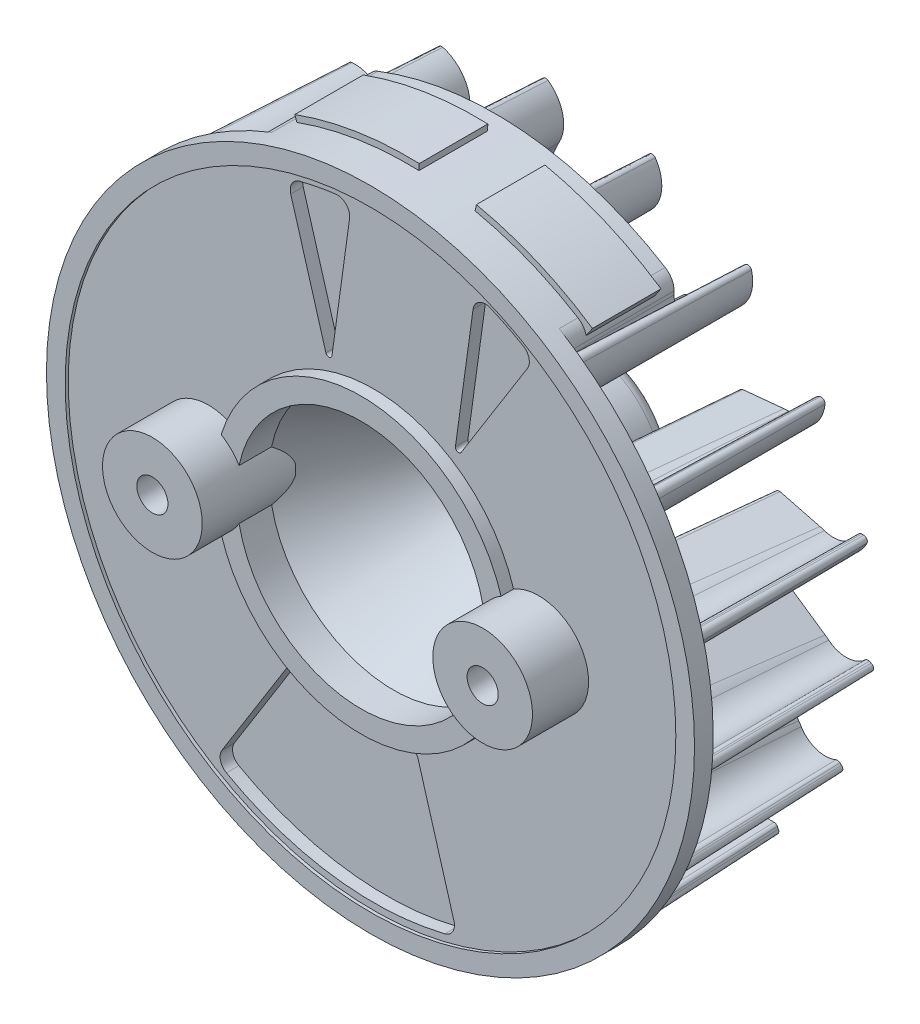
SolidWorks part; units mm, degrees
note: '?' marks a value the reader was unsure of.
ref_plane "Plan1" through (0, 0, 0) normal (0, 0, 1) x (1, 0, 0)
ref_plane "Plan2" through (0, 0, 0) normal (0, 1, 0) x (1, 0, 0)
ref_plane "Plan3" through (0, 0, 0) normal (1, 0, 0) x (0, 0, -1)
sketch "Esquisse1" plane through (0, 0, 0) normal (0, 0, 1) x (1, 0, 0)
  circle A0 centre (0, 0) radius 13
  dimension "D1" = 26
extrude "Base-Extrusion" add sketch "Esquisse1" along normal blind 33
sketch "Esquisse2" plane through (0, 0, 33) normal (0, 0, 1) x (1, 0, 0)
  circle A0 centre (0, 0) radius 52
  dimension "D1" = 104
extrude "Boss.-Extru.1" add sketch "Esquisse2" along normal blind 3
sketch "Esquisse3" plane through (0, 0, 33) normal (0, 0, -1) x (-1, 0, 0)
  line L0 (2.2116, 39.1745) -> (4.5884, 33.9114)
  line L1 (3.9578, 40.1672) -> (6.4523, 34.6434)
  line L2 (4.3511, 50.3505) -> (4.3846, 50.1223)
  line L3 (5.9114, 33.4116) -> (6.0025, 33.4527)
  arc A0 (2.9098, 50.9313) -> (1.3276, 40.7395) centre (7.5, 45) ccw
  arc A1 (4.3511, 50.3505) -> (2.9098, 50.9313) centre (3.4607, 50.2195) ccw
  arc A2 (4.0575, 49.2895) -> (3.0092, 41.8247) centre (7.5, 45) ccw
  arc A3 (4.0575, 49.2895) -> (4.3846, 50.1223) centre (3.4942, 49.9914) ccw
  arc A5 (5.9114, 33.4116) -> (4.5884, 33.9114) centre (5.4998, 34.323) cw
  arc A6 (6.4523, 34.6434) -> (6.0025, 33.4527) centre (5.6321, 34.273) cw
  arc A7 (2.2116, 39.1745) -> (1.3276, 40.7395) centre (-6.9022, 35.0588) ccw
  arc A8 (3.9578, 40.1672) -> (3.0092, 41.8247) centre (-5.1559, 36.0514) ccw
  point P12 (4.3707, 51.816)
  point P17 (5, 33)
  dimension "D3" = 15
  dimension "D7" = 0.9
  dimension "D8" = 1
  dimension "D9" = 0.9
  dimension "D10" = 10
  dimension "D1" = 45
  dimension "D2" = 7.5
  dimension "D4" = 5
  dimension "D5" = 33
  dimension "D6" = 2
ref_plane "Plan4" through (0, 0, 5) normal (0, 0, -1) x (-1, 0, 0)
sketch "Esquisse4" plane through (0, 0, 5) normal (0, 0, -1) x (-1, 0, 0)
  line L0 (1.1226, 41.3554) -> (3.7525, 35.5466)
  line L2 (4.5466, 35.2475) -> (4.8199, 35.3712)
  line L3 (3.4375, 49.5018) -> (3.5019, 49.1763)
  line L4 (5.1185, 36.1663) -> (2.3802, 42.1843)
  arc A0 (2.4988, 49.8725) -> (0.7548, 42.0866) centre (6, 45) ccw
  arc A1 (3.2765, 48.5822) -> (2.0519, 42.8408) centre (6, 45) ccw
  arc A2 (3.4375, 49.5018) -> (2.4988, 49.8725) centre (2.8489, 49.3853) ccw
  arc A3 (3.2765, 48.5822) -> (3.5019, 49.1763) centre (2.9133, 49.0598) ccw
  arc A4 (4.8199, 35.3712) -> (5.1185, 36.1663) centre (4.5724, 35.9178) ccw
  arc A5 (3.7525, 35.5466) -> (4.5466, 35.2475) centre (4.2991, 35.7941) ccw
  arc A6 (0.7548, 42.0866) -> (1.1226, 41.3554) centre (-7.9872, 37.231) cw
  arc A7 (2.0519, 42.8408) -> (2.3802, 42.1843) centre (-6.7218, 38.0426) cw
  point P18 (4, 35)
  dimension "D1" = 12
  dimension "D2" = 45
  dimension "D3" = 6
  dimension "D7" = 0.6
  dimension "D8" = 0.6
  dimension "D9" = 10
  dimension "D10" = 10
  dimension "D4" = 35
  dimension "D5" = 4
  dimension "D6" = 1.5
loft "Boss.-Lissage1" add profiles "Esquisse3", "Esquisse4"
ref_axis "Axe1" through (0, 0, -50) along (0, 0, 1)?
pattern_circular "Répétition circulaire1" count 18 over 360 about axis through (0, 0, -50) along (0, 0, 1)
sketch "Esquisse6" plane through (0, 0, 33) normal (0, 0, -1) x (-1, 0, 0)
  line L0 (-24.8935, 34.1273) -> (-16.7651, 28.6384)
  line L1 (-28.7181, 41.1538) -> (-28.7181, 41.7082)
  line L2 (20.7305, 45.6796) -> (20.7305, 45.5102)
  line L3 (15.8737, 39.3222) -> (10.1445, 31.2739)
  line L4 (-24, 39) -> (20.7305, 40.5102) construction
  line L5 (0, 0) -> (-4.0114, 39.6749) construction
  line L6 (9.2432, 27.8713) -> (14.5886, -24.9977)
  line L7 (-9.2432, -27.8713) -> (-14.5886, 24.9977)
  line L9 (24.8935, -34.1273) -> (16.7651, -28.6384)
  line L10 (28.7181, -40.9224) -> (28.7181, -41.7082)
  line L11 (-20.7305, -45.6796) -> (-20.7305, -45.5102)
  line L12 (-15.8737, -39.3222) -> (-10.1445, -31.2739)
  line L16 (24, -39) -> (-20.7305, -40.5102) construction
  line L17 (0, 0) -> (4.0114, -39.6749) construction
  arc A0 (-28.8366, 40.0719) -> (-24.8935, 34.1273) centre (-24, 39) ccw
  arc A1 (18.8161, 48.4763) -> (-27.2927, 44.2618) centre (0, 0) ccw
  arc A2 (20.7305, 45.5102) -> (15.8737, 39.3222) centre (20.7305, 40.5102) ccw
  arc A3 (28.8071, -40.1973) -> (24.8935, -34.1273) centre (24, -39) ccw
  arc A4 (-18.8161, -48.4763) -> (27.2927, -44.2618) centre (0, 0) ccw
  arc A5 (-20.7305, -45.5102) -> (-15.8737, -39.3222) centre (-20.7305, -40.5102) ccw
  arc A6 (-28.7181, 41.1538) -> (-28.8366, 40.0719) centre (-33.7181, 41.1538) cw
  arc A7 (-27.2927, 44.2618) -> (-28.7181, 41.7082) centre (-25.7181, 41.7082) ccw
  arc A8 (-14.5886, 24.9977) -> (-16.7651, 28.6384) centre (-19.5632, 24.4947) ccw
  arc A9 (-10.1445, -31.2739) -> (-9.2432, -27.8713) centre (-14.2178, -28.3742) ccw
  arc A10 (-18.8161, -48.4763) -> (-20.7305, -45.6796) centre (-17.7305, -45.6796) cw
  arc A11 (28.7181, -41.7082) -> (27.2927, -44.2618) centre (25.7181, -41.7082) cw
  arc A12 (28.8071, -40.1973) -> (28.7181, -40.9224) centre (31.7181, -40.9224) ccw
  arc A13 (14.5886, -24.9977) -> (16.7651, -28.6384) centre (19.5632, -24.4947) ccw
  arc A14 (10.1445, 31.2739) -> (9.2432, 27.8713) centre (14.2178, 28.3742) ccw
  arc A15 (18.8161, 48.4763) -> (20.7305, 45.6796) centre (17.7305, 45.6796) cw
  point P33 (-14.8242, 27.3278)
  point P45 (9.0541, 29.742)
  dimension "D1" = 10
  dimension "D4" = 5
  dimension "D5" = 3
  dimension "D6" = 5
  dimension "D7" = 3
  dimension "D8" = 5
  dimension "D9" = 3
  dimension "D2" = 44.756
  dimension "D3" = 20
extrude "Boss.-Extru.2" add sketch "Esquisse6" along normal blind 17
ref_plane "Plan5" through (0, 0, 30) normal (0, 0, -1) x (-1, 0, 0)
sketch "Esquisse7" plane through (0, 0, 30) normal (0, 0, -1) x (-1, 0, 0)
  line L0 (-27.797, 41.2471) -> (-29.6192, 43.9511)
  line L1 (-10.3215, 48.6566) -> (-10.9981, 51.8463)
  line L2 (-1.7155, 49.7097) -> (-1.828, 52.9685)
  line L3 (17.031, 46.7327) -> (18.1475, 49.7963)
  arc A0 (18.1475, 49.7963) -> (-1.828, 52.9685) centre (0, 0) ccw
  arc A1 (17.031, 46.7327) -> (-1.7155, 49.7097) centre (0, 0) ccw
  arc A2 (-10.9981, 51.8463) -> (-29.6192, 43.9511) centre (0, 0) ccw
  arc A3 (-10.3215, 48.6566) -> (-27.797, 41.2471) centre (0, 0) ccw
  dimension "D1" = 106
extrude "Boss.-Extru.3" add sketch "Esquisse7" along normal blind 11
sketch "Esquisse8" plane through (0, 0, 0) normal (0, 1, 0) x (1, 0, 0)
  line L0 (0, 4.2926) -> (0, -42.7539) construction
  line L1 (0, -33) -> (0, 0) construction
  line L2 (-13.6375, -11.9241) -> (-24.0115, -30.4491)
  line L3 (-26, -34) -> (-12, -34)
  line L4 (-12, -34) -> (-12, -9)
  line L6 (-28.3856, -33.006) -> (-31, -33)
  line L7 (-18.8161, -33) -> (-52, -33) construction
  line L8 (-31, -33) -> (-31.0023, -34)
  line L9 (-31.0023, -34) -> (-26, -34)
  line L10 (-12, -9) -> (-12, -6)
  line L11 (-12, -6) -> (-13, -6)
  line L12 (-13, -6) -> (-13, -9.481)
  arc A0 (-24.0115, -30.4491) -> (-28.3856, -33.006) centre (-28.374, -28.006) cw
  arc A1 (-13, -9.481) -> (-13.6375, -11.9241) centre (-18, -9.481) cw
  dimension "D3" = 5
  dimension "D1" = 9
  dimension "D2" = 26
revolve "Boss.-Révol.1" add sketch "Esquisse8" angle 360 about L0
sketch "Esquisse9" plane through (0, 0, 0) normal (0, 1, 0) x (1, 0, 0)
  line L1 (-6, 4) -> (0, 4)
  line L2 (-6, 4) -> (-6, -7)
  line L5 (-6, -7) -> (-5, -7)
  line L6 (-5, -7) -> (-5, -9)
  line L9 (-10, -9) -> (-5, -9)
  line L10 (-10, -9) -> (-10, -13)
  line L15 (0, 5.3023) -> (0, -39) construction
  line L16 (0, -30) -> (0, -19) construction
  line L17 (-10, -13) -> (-20, -32.2829)
  line L19 (-20, -36) -> (-20, -32.2829)
  line L20 (-52, -36) -> (52, -36) construction
  line L21 (0, 4) -> (0, -36)
  line L23 (0, -36) -> (-20, -36)
  dimension "D1" = 6
  dimension "D2" = 5
  dimension "D3" = 10
  dimension "D4" = 7
  dimension "D7" = 20
revolve "Enlèvement de matière-Révolution1" cut sketch "Esquisse9" angle 360 about L15
sketch "Esquisse10" plane through (0, 0, 0) normal (0, 0, -1) x (-1, 0, 0)
  line L1 (-2.4503, 3.2689) -> (-5.1757, 4.9459)
  line L2 (-4.0225, 0.7139) -> (-6.7479, 2.3909)
  line L3 (-2.4503, 3.2689) -> (-4.0225, 0.7139)
  line L4 (-5.1757, 4.9459) -> (-6.7479, 2.3909)
  dimension "D1" = 3.8
  dimension "D2" = 7
  dimension "D3" = 3
  dimension "D4" = 1.5
extrude "Enlèv. mat.-Extru.1" cut sketch "Esquisse10" against normal through all
sketch "Esquisse12" plane through (0, 0, 36) normal (0, 0, 1) x (1, 0, 0)
  circle A0 centre (0, 0) radius 49
  dimension "D1" = 98
extrude "Enlèv. mat.-Extru.2" cut sketch "Esquisse12" against normal blind 0.5
sketch "Esquisse13" plane through (0, 0, 35.5) normal (0, 0, 1) x (1, 0, 0)
  circle A0 centre (0, 0) radius 23.5
  circle A1 centre (0, 0) radius 20
  dimension "D1" = 47
extrude "Boss.-Extru.4" add sketch "Esquisse13" along normal blind 2
ref_plane "Plan6" through (0, 0, 44.5) normal (0, 0, 1) x (1, 0, 0)
sketch "Esquisse15" plane through (0, 0, 44.5) normal (0, 0, 1) x (1, 0, 0)
  line L0 (-26.5, 0) -> (26.5, 0) construction
  circle A0 centre (26.5, 0) radius 8
  circle A1 centre (-26.5, 0) radius 8
  dimension "D1" = 16
  dimension "D2" = 16
  dimension "D4" = 26.5
  dimension "D3" = 26.5
extrude "Boss.-Extru.7" add sketch "Esquisse15" against normal blind 15
sketch "Esquisse16" plane through (0, 0, 44.5) normal (0, 0, 1) x (1, 0, 0)
  circle A0 centre (-26.5, 0) radius 2.5
  circle A1 centre (26.5, 0) radius 2.5
  dimension "D1" = 5
  dimension "D2" = 5
extrude "Enlèv. mat.-Extru.3" cut sketch "Esquisse16" against normal blind 15
cosmetic thread "Représentation de filetage1" parameters "D1"=15, "D2"=7
sketch "Esquisse17" plane through (0, 0, 35.5) normal (0, 0, 1) x (1, 0, 0)
  line L0 (0, 0) -> (8.1354, 58.9815) construction
  line L1 (13.1309, 22.0125) -> (15.9611, 42.5316)
  line L2 (-6.6815, 24.7452) -> (-3.8513, 45.2643)
  line L3 (-7.6567, 24.673) -> (-13.2943, 43.9158)
  line L4 (14.0501, 21.6789) -> (24.6864, 38.6771)
  line L5 (7.1474, -24.396) -> (12.8955, -44.0159)
  line L6 (-13.4848, -21.5502) -> (-24.3296, -38.8814)
  arc A0 (23.9926, 41.4691) -> (18.724, 44.0992) centre (0, 0) ccw
  arc A1 (-11.8705, 46.4157) -> (-13.2943, 43.9158) centre (-11.375, 44.4781) ccw
  arc A2 (-10.8647, -20.8377) -> (4.818, -23.0008) centre (0, 0) ccw
  arc A3 (-23.6202, -41.6824) -> (11.4543, -46.5202) centre (0, 0) ccw
  arc A4 (-6.0867, 47.5214) -> (-11.8705, 46.4157) centre (0, 0) ccw
  arc A5 (-6.0867, 47.5214) -> (-3.8513, 45.2643) centre (-5.8326, 45.5376) cw
  arc A6 (18.724, 44.0992) -> (15.9611, 42.5316) centre (17.9423, 42.2583) ccw
  arc A7 (24.6864, 38.6771) -> (23.9926, 41.4691) centre (22.991, 39.738) ccw
  arc A8 (4.818, -23.0008) -> (7.1474, -24.396) centre (5.228, -24.9583) cw
  arc A9 (-13.4848, -21.5502) -> (-10.8647, -20.8377) centre (-11.7893, -22.6111) cw
  arc A10 (-23.6202, -41.6824) -> (-24.3296, -38.8814) centre (-22.6341, -39.9423) cw
  arc A11 (12.8955, -44.0159) -> (11.4543, -46.5202) centre (10.9761, -44.5782) cw
  arc A12 (-6.6815, 24.7452) -> (-7.6567, 24.673) centre (-7.1769, 24.8136) cw
  arc A13 (14.0501, 21.6789) -> (13.1309, 22.0125) centre (13.6262, 21.9442) cw
  point P15 (-13.8639, 45.8598)
  point P18 (-3.5042, 47.7813)
  point P21 (16.3083, 45.0485)
  point P24 (25.761, 40.3943)
  point P27 (6.6071, -22.5521)
  point P30 (-12.4655, -19.9213)
  point P33 (-25.4136, -40.6138)
  point P36 (13.47, -45.9771)
  point P39 (-7.0005, 22.4331)
  point P42 (12.812, 19.7003)
  dimension "D1" = 2
  dimension "D2" = 2
  dimension "D4" = 0.5
  dimension "D3" = 10
extrude "Enlèv. mat.-Extru.4" cut sketch "Esquisse17" against normal blind 2
fillet "Congé3" radius 2
